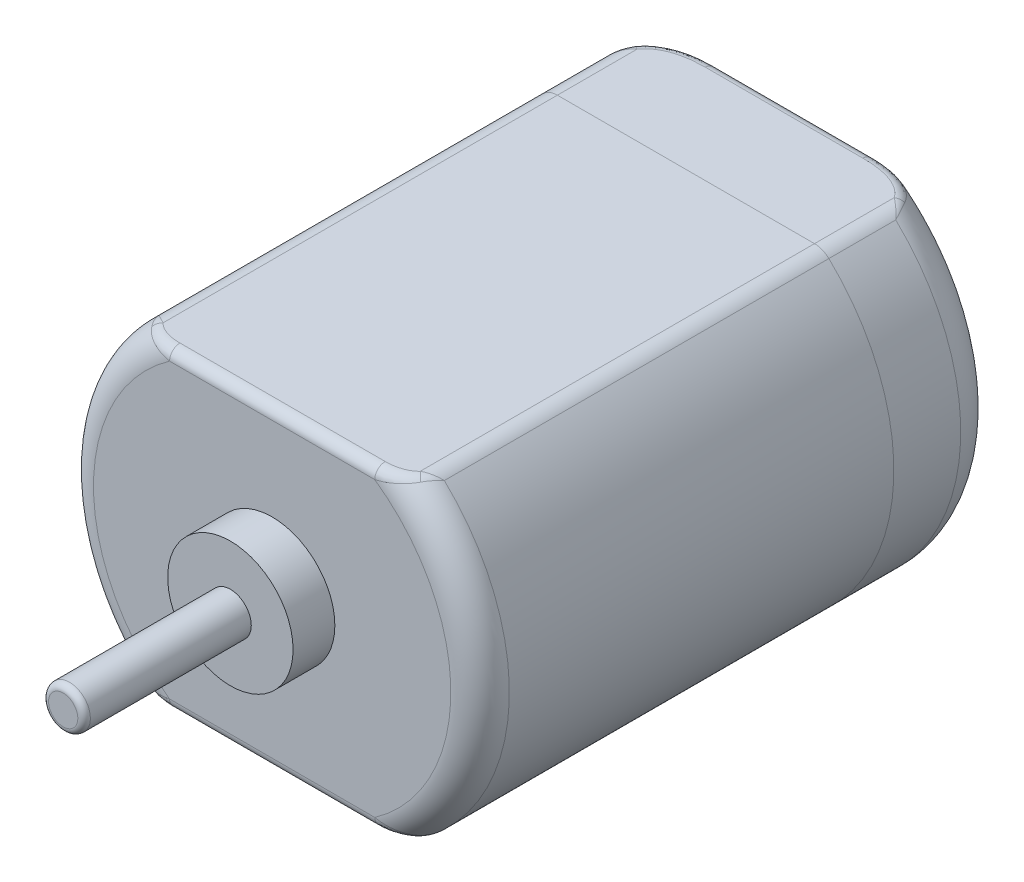
SolidWorks part; units mm, degrees
ref_plane "Front Plane" through (0, 0, 0) normal (0, 0, 1) x (1, 0, 0)
ref_plane "Top Plane" through (0, 0, 0) normal (0, 1, 0) x (1, 0, 0)
ref_plane "Right Plane" through (0, 0, 0) normal (1, 0, 0) x (0, 0, -1)
sketch "Sketch1" plane through (0, 0, 0) normal (0, 0, 1) x (1, 0, 0)
  line L0 (0, 7.5) -> (0, -7.5) construction
  line L1 (-6.5385, 7.5) -> (0, 7.5)
  line L2 (0, 7.5) -> (6.5385, 7.5)
  line L3 (-6.5385, -7.5) -> (0, -7.5)
  line L4 (0, -7.5) -> (6.5385, -7.5)
  arc A0 (6.5385, -7.5) -> (6.5385, 7.5) centre (0, 0) ccw
  arc A1 (-6.5385, 7.5) -> (-6.5385, -7.5) centre (0, 0) ccw
  point P5 (0, 0)
  dimension "D1" = 19.9
  dimension "D2" = 15
extrude "Boss-Extrude1" add sketch "Sketch1" along normal blind 19.8
fillet "Fillet1" radius 1 4 edges at (6.5385, -7.5, 9.9) (-6.5385, -7.5, 9.9) (-6.5385, 7.5, 9.9) (6.5385, 7.5, 9.9)
fillet "Fillet2" radius 1.4 2 edges at (9.95, 0, 19.8) (-9.95, 0, 19.8)
sketch "Sketch3" plane through (0, 0, 19.8) normal (0, 0, 1) x (1, 0, 0)
  circle A0 centre (0, 0) radius 3
  dimension "D1" = 6
extrude "Boss-Extrude2" add sketch "Sketch3" along normal blind 2 contours A0
sketch "Sketch4" plane through (0, 0, 21.8) normal (0, 0, 1) x (1, 0, 0)
  circle A0 centre (0, 0) radius 1
  dimension "D1" = 2
extrude "Boss-Extrude3" add sketch "Sketch4" along normal blind 8
fillet "Fillet3" radius 0.3 1 edges at (1, 0, 29.8)
sketch "Sketch5" plane through (0, 0, 0) normal (0, 0, -1) x (-1, 0, 0)
  line L2 (-6.1524, -7.5) -> (6.1524, -7.5)
  line L6 (-6.1524, -7.5) -> (6.1524, -7.5)
  line L8 (6.1524, 7.5) -> (-6.1524, 7.5)
  line L9 (6.1524, 7.5) -> (-6.1524, 7.5)
  arc A6 (-6.8399, 7.2263) -> (-6.8399, -7.2263) centre (0, 0) ccw
  arc A8 (-6.8399, 7.2263) -> (-6.8399, -7.2263) centre (0, 0) ccw
  arc A10 (-6.8399, -7.2263) -> (-6.1524, -7.5) centre (-6.1524, -6.5) ccw
  arc A18 (-6.8399, -7.2263) -> (-6.1524, -7.5) centre (-6.1524, -6.5) ccw
  arc A20 (6.1524, -7.5) -> (6.8399, -7.2263) centre (6.1524, -6.5) ccw
  arc A22 (6.1524, -7.5) -> (6.8399, -7.2263) centre (6.1524, -6.5) ccw
  arc A24 (6.8399, -7.2263) -> (6.8399, 7.2263) centre (0, 0) ccw
  arc A25 (6.8399, -7.2263) -> (6.8399, 7.2263) centre (0, 0) ccw
  arc A26 (6.8399, 7.2263) -> (6.1524, 7.5) centre (6.1524, 6.5) ccw
  arc A27 (6.8399, 7.2263) -> (6.1524, 7.5) centre (6.1524, 6.5) ccw
  arc A28 (-6.1524, 7.5) -> (-6.8399, 7.2263) centre (-6.1524, 6.5) ccw
  arc A29 (-6.1524, 7.5) -> (-6.8399, 7.2263) centre (-6.1524, 6.5) ccw
  dimension "D1" = 0
extrude "Boss-Extrude4" add sketch "Sketch5" along normal blind 5.2 separate body
fillet "Fillet6" radius 0.5 10 edges at (-6.5894, -7.3995, 18.7396) (-5.5052, -7.5, 19.5799) (6.5894, -7.3995, 18.7396) (5.5409, -7.5, 19.5661) (6.5894, 7.3995, 18.7396) (5.5052, 7.5, 19.5799) (-6.5894, 7.3995, 18.7396) (-5.5409, 7.5, 19.5661) (0, -7.5, 19.8) (0, 7.5, 19.8)
sketch "Sketch6" plane through (0, 0, -5.2) normal (0, 0, -1) x (-1, 0, 0)
  line L0 (0, 0) -> (0, 3.5) construction
  line L1 (-3.4293, 3.5) -> (-0.1824, 3.5)
  line L2 (-0.1824, 3.5) -> (0, 3.5)
  line L3 (0, 3.5) -> (3.4293, 3.5)
  arc A0 (-3.4293, 3.5) -> (3.4293, 3.5) centre (0, 0) ccw
  dimension "D1" = 9.8
  dimension "D2" = 3.5
extrude "Boss-Extrude5" add sketch "Sketch6" along normal blind 2.1
sketch "Sketch7" plane through (0, 0, -7.3) normal (0, 0, -1) x (-1, 0, 0)
  circle A0 centre (0, 0) radius 1
  dimension "D1" = 2
extrude "Boss-Extrude6" add sketch "Sketch7" along normal blind 1 separate body
fillet "Fillet8" radius 0.2 1 edges at (-1, 0, -8.3)
fillet "Fillet9" radius 0.2 2 edges at (0, 3.5, -7.3) (0, -4.9, -7.3)
sketch "Sketch8" plane through (0, -7.5, 0) normal (0, -1, 0) x (1, 0, 0)
  line L0 (-6.1524, 0) -> (6.1524, -5.2) construction
  line L1 (-6.1524, 0) -> (6.1524, 0) construction
  line L2 (-4, -5.2) -> (4, -5.2)
  line L3 (-4, -5.2) -> (-4, 0)
  line L4 (-4, 0) -> (4, 0)
  line L5 (4, -5.2) -> (4, 0)
  line L6 (-4, -5.2) -> (4, 0) construction
  line L7 (-4, 0) -> (4, -5.2) construction
  point P4 (0, -2.6)
  dimension "D1" = 8
extrude "Boss-Extrude7" add sketch "Sketch8" along normal blind 1.6 separate body
combine bodies "Combine1" operation type add bodies to combine 105 107
fillet "Fillet10" radius 2 1 edges at (-9.95, 0, -5.2)
fillet "Fillet11" radius 0.5 5 edges at (-6.6378, 7.3743, -3.5351) (-4.7501, 7.5, -4.9718) (6.6378, 7.3743, -3.5351) (5.506, 7.5, -4.6719) (0, 7.5, -5.2)
